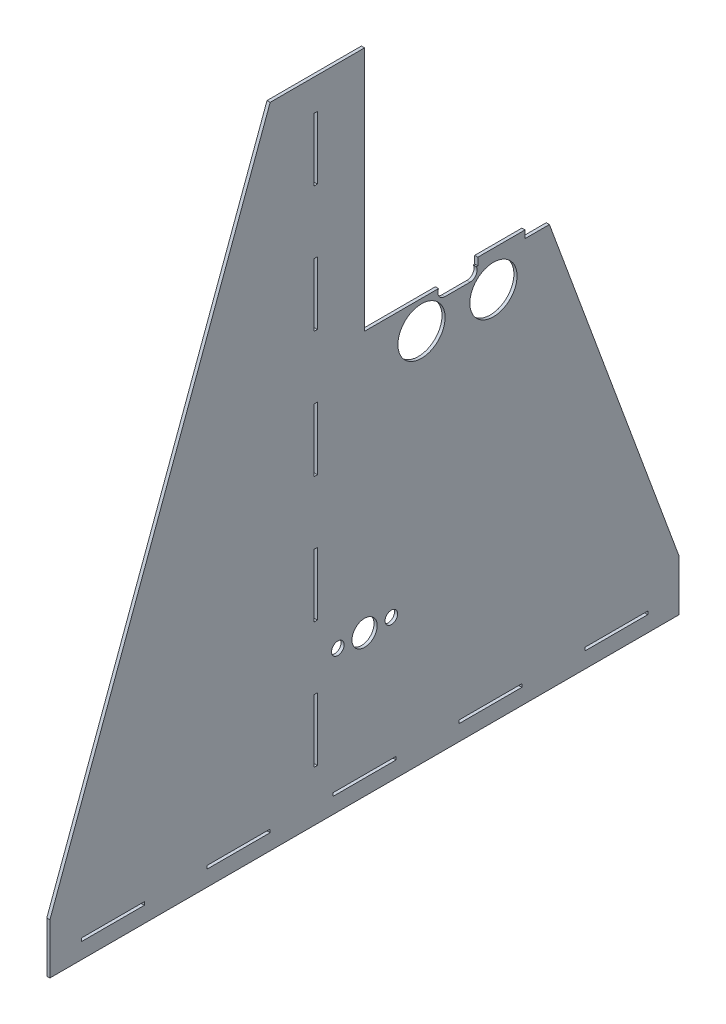
SolidWorks part; units mm, degrees
ref_plane "Přední rovina" through (0, 0, 0) normal (0, 0, 1) x (1, 0, 0)
ref_plane "Horní rovina" through (0, 0, 0) normal (0, 1, 0) x (1, 0, 0)
ref_plane "Pravá rovina" through (0, 0, 0) normal (1, 0, 0) x (0, 0, -1)
sketch "Skica1" plane through (0, 0, 0) normal (1, 0, 0) x (0, 0, -1)
  line L0 (0, 0) -> (0, 200)
  line L1 (-100, 0) -> (100, 0)
  line L2 (-100, 0) -> (-100, 206)
  line L3 (-100, 206) -> (100, 206)
  line L4 (100, 0) -> (100, 206)
  line L5 (-90, 5) -> (-70, 5)
  line L6 (-90, 5) -> (-90, 6)
  line L7 (-90, 6) -> (-70, 6)
  line L8 (-70, 5) -> (-70, 6)
  line L9 (-50, 5) -> (-30, 5)
  line L10 (-50, 5) -> (-50, 6)
  line L11 (-50, 6) -> (-30, 6)
  line L12 (-30, 5) -> (-30, 6)
  line L13 (-10, 5) -> (10, 5)
  line L14 (-10, 5) -> (-10, 6)
  line L15 (-10, 6) -> (10, 6)
  line L16 (10, 5) -> (10, 6)
  line L17 (50, 6) -> (30, 6)
  line L18 (30, 5) -> (30, 6)
  line L19 (50, 5) -> (30, 5)
  line L20 (50, 5) -> (50, 6)
  line L21 (90, 6) -> (70, 6)
  line L22 (70, 5) -> (70, 6)
  line L23 (90, 5) -> (70, 5)
  line L24 (90, 5) -> (90, 6)
  line L25 (-8.5, 45) -> (0, 45)
  line L26 (0, 200) -> (0, 206)
  line L27 (-15, 16) -> (-16, 16)
  line L28 (-15, 16) -> (-15, 36)
  line L29 (-15, 36) -> (-16, 36)
  line L30 (-16, 16) -> (-16, 36)
  line L31 (-15, 56) -> (-16, 56)
  line L32 (-15, 56) -> (-15, 76)
  line L33 (-15, 76) -> (-16, 76)
  line L34 (-16, 56) -> (-16, 76)
  line L35 (-15, 96) -> (-16, 96)
  line L36 (-15, 96) -> (-15, 116)
  line L37 (-15, 116) -> (-16, 116)
  line L38 (-16, 96) -> (-16, 116)
  line L39 (-15, 136) -> (-16, 136)
  line L40 (-15, 136) -> (-15, 156)
  line L41 (-15, 156) -> (-16, 156)
  line L42 (-16, 136) -> (-16, 156)
  line L43 (-15, 176) -> (-16, 176)
  line L44 (-15, 176) -> (-15, 196)
  line L45 (-15, 196) -> (-16, 196)
  line L46 (-16, 176) -> (-16, 196)
  line L47 (-30, 206) -> (-100, 16)
  line L48 (100, 16) -> (30, 206)
  line L49 (58.7368, 128) -> (0, 128)
  line L50 (25.5223, 127) -> (33.5223, 127) construction
  line L51 (36, 128) -> (51, 128)
  line L52 (36, 128) -> (36, 130.3908)
  line L53 (36, 130.3908) -> (51, 130.3908)
  line L54 (51, 128) -> (51, 130.3908)
  line L55 (25.5223, 129.25) -> (33.5223, 129.25)
  line L56 (25.5223, 124.75) -> (33.5223, 124.75)
  circle A0 centre (0, 45) radius 4
  circle A1 centre (-8.5, 45) radius 2
  circle A2 centre (8.5, 45) radius 2
  circle A3 centre (18.0923, 119) radius 7.5
  circle A4 centre (40.9523, 119) radius 7.5
  arc A5 (25.5223, 129.25) -> (25.5223, 124.75) centre (25.5223, 127) ccw
  arc A6 (33.5223, 124.75) -> (33.5223, 129.25) centre (33.5223, 127) ccw
  point P19 (-30, 5.5)
  point P20 (-70, 5.5)
  point P21 (-80, 6)
  point P56 (-15.5, 176)
  point P57 (-30, 206)
  point P59 (30, 206)
  point P76 (29.5223, 127)
  point P82 (0, 0)
  dimension "D13" = 8
  dimension "D15" = 4
  dimension "D31" = 15
  dimension "D33" = 8
  dimension "D37" = 8
  dimension "D1" = 200
  dimension "D2" = 100
  dimension "D3" = 206
  dimension "D4" = 20
  dimension "D5" = 10
  dimension "D6" = 20
  dimension "D7" = 20
  dimension "D8" = 20
  dimension "D9" = 20
  dimension "D10" = 1
  dimension "D11" = 5
  dimension "D12" = 0
  dimension "D14" = 8.5
  dimension "D16" = 40
  dimension "D17" = 10
  dimension "D18" = 20
  dimension "D19" = 20
  dimension "D20" = 20
  dimension "D21" = 20
  dimension "D22" = 20
  dimension "D23" = 20
  dimension "D24" = 20
  dimension "D25" = 20
  dimension "D26" = 20
  dimension "D27" = 1
  dimension "D28" = 15
  dimension "D29" = 30
  dimension "D30" = 22.86
  dimension "D32" = 74
  dimension "D34" = 36
  dimension "D35" = 15
  dimension "D36" = 73.7368
  dimension "D38" = 11.43
  dimension "D39" = 8
  dimension "D40" = 4.5
extrude "Přidat vysunutím1" add sketch "Skica1" along normal blind 1 contours L14 L15 L0 L3 L2 L1 L13 L12 L9 L10 L11 L8 L5 L6 L7 | L16 L13 L0 L1 L4 L3 L15 L24 L23 L22 L21 L20 L19 L18 L17 | L53 L54 L51 L52 region at (0, 84.3242, 37.495) region at (0, 56.027, -42.6126)
